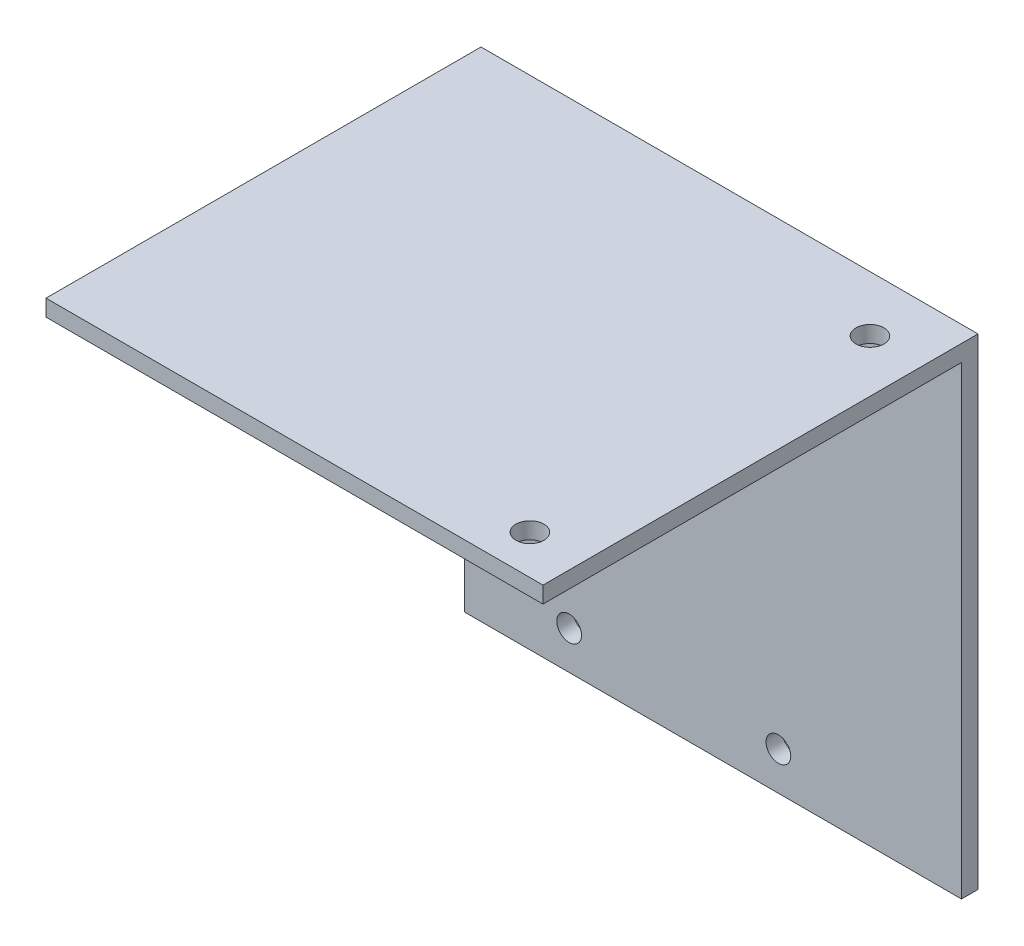
SolidWorks part; units mm, degrees
ref_plane "Front Plane" through (0, 0, 0) normal (0, 0, 1) x (1, 0, 0)
ref_plane "Top Plane" through (0, 0, 0) normal (0, 1, 0) x (1, 0, 0)
ref_plane "Right Plane" through (0, 0, 0) normal (1, 0, 0) x (0, 0, -1)
sketch "Sketch1" plane through (0, 0, 0) normal (0, 0, 1) x (1, 0, 0)
  line L0 (38.1, 51.75) -> (12.7, 51.75) construction
  line L1 (0, 58.4) -> (60.325, 58.4)
  line L2 (0, 58.4) -> (0, 0)
  line L3 (0, 0) -> (60.325, 0)
  line L4 (60.325, 58.4) -> (60.325, 0)
  line L6 (12.7, 51.75) -> (12.7, 4.65) construction
  line L8 (12.7, 4.65) -> (38.1, 4.65) construction
  line L9 (38.1, 51.75) -> (38.1, 4.65) construction
  circle A4 centre (12.7, 51.75) radius 1.5
  circle A5 centre (38.1, 51.75) radius 1.5
  circle A6 centre (12.7, 4.65) radius 1.5
  circle A7 centre (38.1, 4.65) radius 1.5
  point P5 (0, 0)
  point P7 (0, 0)
  dimension "D3" = 3
  dimension "D1" = 58.4
  dimension "D2" = 60.325
  dimension "D4" = 47.1
  dimension "D6" = 4.65
  dimension "D7" = 25.4
  dimension "D9" = 12.7
extrude "Boss-Extrude1" add sketch "Sketch1" against normal blind 2
sketch "Sketch2" plane through (0, 0, -2) normal (0, 0, -1) x (-1, 0, 0)
  line L0 (0, 58.4) -> (0, 56.4)
  line L1 (0, 58.4) -> (0, 0) construction
  line L2 (0, 56.4) -> (-60.325, 56.4)
  line L3 (-60.325, 56.4) -> (-60.325, 58.4)
  line L4 (-60.325, 58.4) -> (0, 58.4) construction
  line L5 (-60.325, 58.4) -> (0, 58.4)
  dimension "D1" = 60.325
  dimension "D2" = 2
extrude "Boss-Extrude2" add sketch "Sketch2" against normal blind 52.8
sketch "Sketch3" plane through (0, 58.4, 0) normal (0, 1, 0) x (1, 0, 0)
  line L0 (53.975, -4.7625) -> (53.975, -46.0375) construction
  line L2 (60.325, -50.8) -> (60.325, 2) construction
  line L3 (0, -50.8) -> (60.325, -50.8) construction
  circle A0 centre (53.975, -4.7625) radius 1.7
  circle A1 centre (53.975, -46.0375) radius 1.7
  dimension "D1" = 3.4
  dimension "D2" = 41.275
  dimension "D3" = 4.7625
  dimension "D4" = 6.35
extrude "Cut-Extrude1" cut sketch "Sketch3" against normal through all
